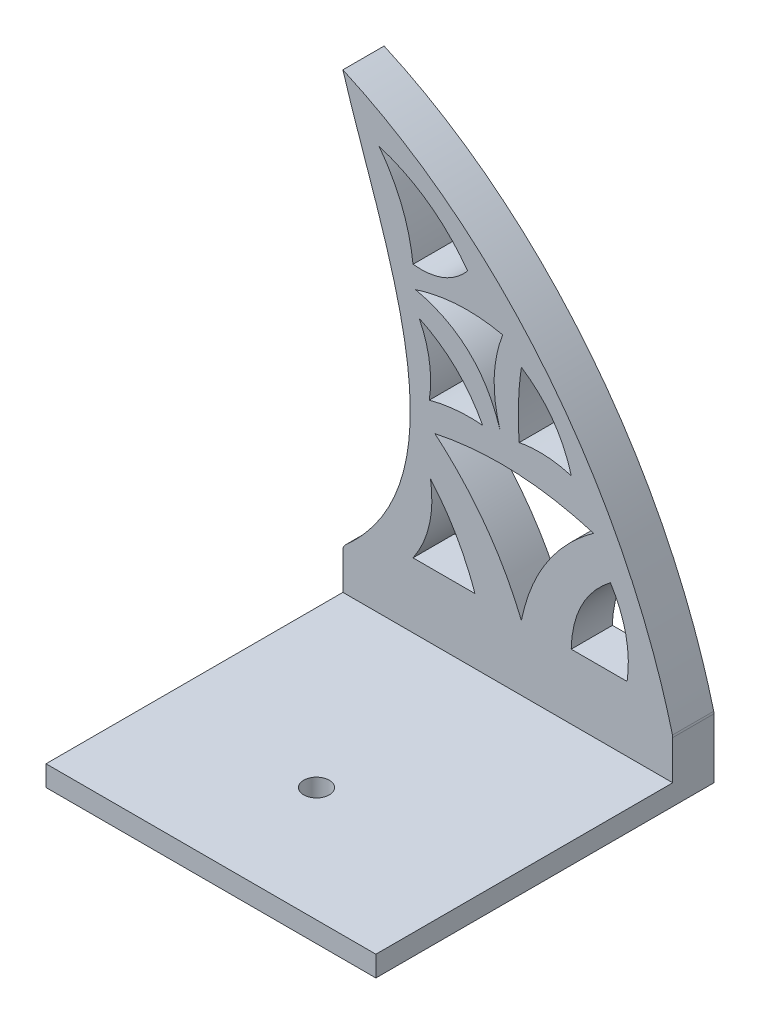
SolidWorks part; units mm, degrees
material "1060 Alloy"
ref_plane "Front Plane" through (0, 0, 0) normal (0, 0, 1) x (1, 0, 0)
ref_plane "Top Plane" through (0, 0, 0) normal (0, 1, 0) x (1, 0, 0)
ref_plane "Right Plane" through (0, 0, 0) normal (1, 0, 0) x (0, 0, -1)
sketch "Sketch1" plane through (0, 0, 0) normal (0, 0, 1) x (1, 0, 0)
  line L1 (0, 0) -> (101.6, 0)
  line L2 (0, 0) -> (0, 152.4)
  line L3 (0, 152.4) -> (101.6, 152.4)
  line L4 (101.6, 0) -> (101.6, 152.4)
  dimension "D1" = 101.6
  dimension "D2" = 152.4
extrude "Boss-Extrude1" add sketch "Sketch1" along normal blind 12.7 contours L2 L1 L4 L3
sketch "Sketch2" plane through (0, 0, 0) normal (0, 0, 1) x (1, 0, 0)
  line L0 (0, 152.4) -> (0, 279.4) construction
  line L1 (0, 152.4) -> (101.6, 152.4)
  line L3 (40.6766, 160.02) -> (21.6029, 160.02)
  line L4 (70.3278, 160.02) -> (87.5465, 160.02)
  spline S0 degree 3 poles (0, 279.4) (51.2861, 256.55) (87.8369, 205.9579) (101.6, 152.4) knots 0 0 0 0 1 1 1 1
  spline S1 degree 3 poles (0, 152.4) (39.7901, 186.8391) (12.3098, 238.8455) (0, 279.4) knots 0 0 0 0 1 1 1 1
  spline S2 degree 2 poles (26.9805, 183.8137) (28.9588, 170.8375) (21.6029, 160.02) knots 0 0 0 1 1 1
  spline S3 degree 2 poles (82.3961, 183.8137) (89.3396, 172.7738) (87.5465, 160.02) knots 0 0 0 1 1 1
  spline S4 degree 2 poles (23.5161, 224.8619) (28.2353, 215.2193) (26.6057, 204.5822) knots 0 0 0 1 1 1
  spline S5 degree 2 poles (54.9771, 227.5573) (66.6459, 219.8522) (70.3283, 206.2775) knots 0 0 0 1 1 1
  spline S6 degree 2 poles (21.6029, 238.3231) (31.8648, 237.2845) (38.4123, 244.9499) knots 0 0 0 1 1 1
  spline S7 degree 2 poles (26.9805, 183.8137) (36.1385, 173.1751) (40.6766, 160.02) knots 0 0 0 1 1 1
  spline S8 degree 2 poles (82.3961, 183.8137) (70.6714, 174.6636) (70.3278, 160.02) knots 0 0 0 1 1 1
  spline S9 degree 2 poles (54.9771, 160.02) (46.0835, 181.5476) (28.3421, 196.5298) knots 0 0 0 1 1 1
  spline S10 degree 2 poles (54.9771, 160.02) (59.3747, 181.4006) (77.1872, 194.3635) knots 0 0 0 1 1 1
  spline S11 degree 2 poles (28.3421, 196.5298) (53.0178, 201.7323) (77.1872, 194.3635) knots 0 0 0 1 1 1
  spline S12 degree 2 poles (26.6057, 204.5822) (34.7004, 206.7929) (43.0535, 206.088) knots 0 0 0 1 1 1
  spline S13 degree 2 poles (43.0535, 206.088) (36.2398, 218.9127) (23.5161, 224.8619) knots 0 0 0 1 1 1
  spline S14 degree 2 poles (70.3283, 206.2775) (62.3616, 208.669) (54.2871, 207.1099) knots 0 0 0 1 1 1
  spline S15 degree 2 poles (54.2871, 207.1099) (53.4821, 217.3917) (54.9771, 227.5573) knots 0 0 0 1 1 1
  spline S16 degree 2 poles (48.4004, 207.5354) (42.0542, 227.5662) (22.3756, 231.9373) knots 0 0 0 1 1 1
  spline S17 degree 2 poles (48.4004, 207.5354) (44.3936, 220.7345) (49.2258, 233.3158) knots 0 0 0 1 1 1
  spline S18 degree 2 poles (49.2258, 233.3158) (35.6412, 236.2679) (22.3756, 231.9373) knots 0 0 0 1 1 1
  spline S19 degree 2 poles (21.6029, 238.3231) (19.952, 252.9745) (11.0947, 264.6015) knots 0 0 0 1 1 1
  spline S20 degree 2 poles (11.0947, 264.6015) (28.0538, 259.2958) (38.4123, 244.9499) knots 0 0 0 1 1 1
  dimension "D1" = 127
extrude "Boss-Extrude3" add sketch "Sketch2" along normal blind 12.7 contours S1 L1 S0 S18 S17 S16 S13 S12 S4 S8 S3 L4 S2 S7 L3 S9 S11 S10 S14 S15 S5 S19 S20 S6 region at (45.9671, 198.7592, 0)
fillet "Fillet1" radius 2.54 2 edges at (101.6, 152.4, 6.35) (0, 152.4, 6.35)
fillet "Fillet2" radius 5.08 2 edges at (101.6, 0, 6.35) (0, 0, 6.35)
sketch "Sketch5" plane through (0, 0, 12.7) normal (0, 0, 1) x (1, 0, 0)
  line L1 (101.519, 133.6639) -> (101.6, 133.6639)
  line L2 (101.6, 5.08) -> (101.6, 152.0778) construction
  line L4 (101.6, 133.6639) -> (0, 133.6639)
  line L5 (101.6, 133.6639) -> (101.6, 0)
  line L6 (101.6, 0) -> (0, 0)
  line L7 (0, 133.6639) -> (0, 0)
  line M2 (5.08, 0) -> (96.52, 0)
  arc M3 (96.52, 0) -> (101.6, 5.08) centre (96.52, 5.08) ccw
  line M4 (101.6, 5.08) -> (101.6, 152.0778)
  line M9 (0, 151.2513) -> (0, 5.08)
  arc M10 (0, 5.08) -> (5.08, 0) centre (5.08, 5.08) ccw
extrude "Cut-Extrude2" cut sketch "Sketch5" against normal through all contours L1 L4 M9 M10 M2 M3 M4 region at (50.8, 66.8856, 12.7)
sketch "Sketch8" plane through (0, 0, 12.7) normal (0, 0, 1) x (1, 0, 0)
  line L0 (0, 133.6639) -> (0, 151.2513) construction
  line L1 (101.6, 133.6639) -> (0, 133.6639)
  line L2 (101.6, 133.6639) -> (101.6, 140.0139)
  line L3 (101.6, 140.0139) -> (0, 140.0139)
  line L4 (0, 133.6639) -> (0, 140.0139)
  dimension "D1" = 6.35
extrude "Boss-Extrude4" add sketch "Sketch8" along normal blind 91.44
sketch "Sketch9" plane through (0, 140.0139, 0) normal (0, 1, 0) x (1, 0, 0)
  line L0 (101.6, -12.7) -> (0, -12.7) construction
  line L3 (101.6, -104.14) -> (101.6, -12.7) construction
  circle A1 centre (48.006, -68.834) radius 3.937
  dimension "D1" = 7.874
  dimension "D2" = 56.134
  dimension "D3" = 53.594
extrude "Cut-Extrude3" cut sketch "Sketch9" against normal through all
